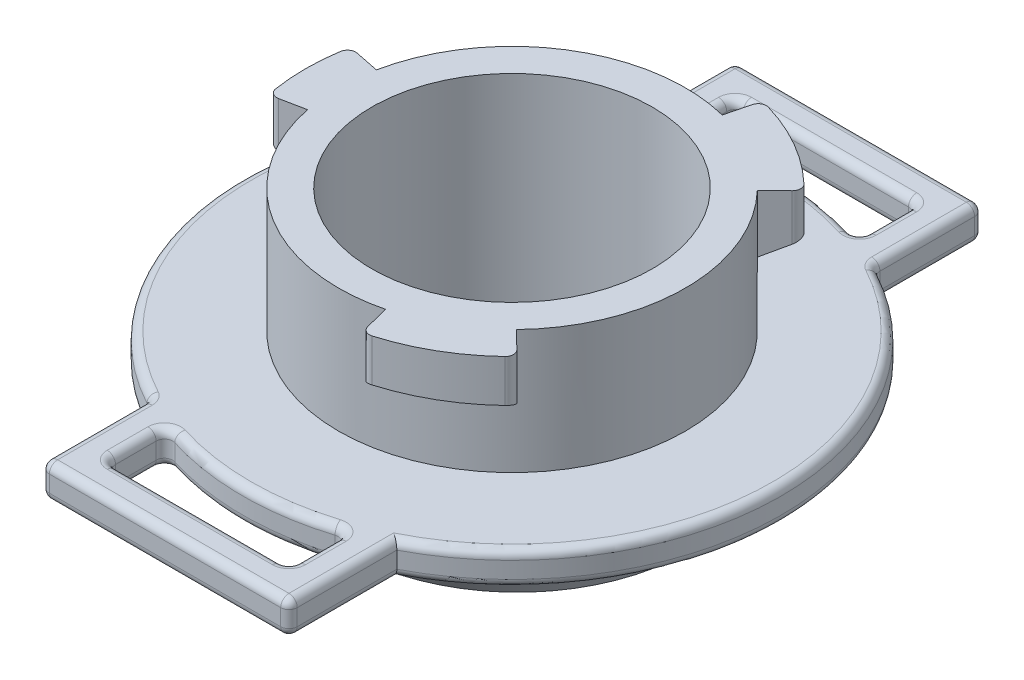
SolidWorks part; units mm, degrees
ref_plane "Front" through (0, 0, 0) normal (0, 0, 1) x (1, 0, 0)
ref_plane "Top" through (0, 0, 0) normal (0, 1, 0) x (1, 0, 0)
ref_plane "Right" through (0, 0, 0) normal (1, 0, 0) x (0, 0, -1)
sketch "Sketch1" plane through (0, 0, 0) normal (0, 0, 1) x (1, 0, 0)
  line L0 (-159.7123, 0) -> (16.3, 0) construction
  line L1 (0, 78.8071) -> (0, -67.8786) construction
  line L2 (9.2, 9.5) -> (9.2, 0)
  line L3 (9.2, 0) -> (16.3, 0)
  line L7 (16.3, 2) -> (10.5, 2)
  line L8 (10.5, 2) -> (10.5, 9.5)
  line L9 (10.5, 9.5) -> (9.2, 9.5)
  line L11 (-10.5, 6) -> (-12.5, 6.9326)
  line L12 (-10.5, 9.5) -> (-12.5, 9.5)
  line L13 (-10.5, 9.5) -> (-10.5, 6)
  line L14 (-10.5, 6) -> (-12.5, 6)
  line L15 (-12.5, 9.5) -> (-12.5, 6)
  line L19 (16.3, 2) -> (16.3, 0)
  line L20 (9.2, 9.5) -> (0, 9.5)
  line L21 (0, 9.5) -> (0, 0)
  line L22 (0, 0) -> (9.2, 0)
  dimension "D10" = 2
  dimension "D1" = 21
  dimension "D2" = 1.3
  dimension "D3" = 7.5
  dimension "D4" = 2
  dimension "D9" = 3.5
  dimension "D11" = 25
revolve "Revolve1" add sketch "Sketch1" angle 360 about L1 region at (9.85, 9.3814, 0) region at (4.6, 4.75, 0)
ref_plane "Plane1" through (0, 2, 0) normal (0, 1, 0) x (1, 0, 0)
sketch "Sketch3" plane through (0, 2, 0) normal (0, 1, 0) x (1, 0, 0)
  line L0 (-23.4994, 0) -> (28.8789, 0) construction
  line L1 (0, 22.41) -> (0, -22.0852) construction
  line L3 (2, 20) -> (3, 20)
  line L4 (2, 20) -> (2, 15)
  line L5 (2, 15) -> (3, 15)
  line L6 (3, 20) -> (3, 15)
  line L7 (-2, 20) -> (-3, 20)
  line L8 (-2, 20) -> (-2, 15)
  line L9 (-2, 15) -> (-3, 15)
  line L10 (-3, 20) -> (-3, 15)
  dimension "D1" = 4
  dimension "D2" = 1
  dimension "D3" = 20
  dimension "D4" = 15
revolve "Revolve2" add sketch "Sketch1<7>" angle 22.9 mid plane about L1 region at (-11.4488, 7.9712, 0)
sketch "Sketch1<7>" plane through (0, 0, 0) normal (0, 0, 1) x (1, 0, 0) same geometry as "Sketch1"
ref_axis "Axis1" through (0, -50, 0) along (0, 1, 0)
ref_plane "Plane2" through (0, 0, 0) normal (-0.866, 0, -0.5) x (0, 1, 0)
sketch "Sketch4" plane through (0, 0, 0) normal (-0.866, 0, -0.5) x (0, 1, 0)
  line L1 (9.5, 10.5) -> (6, 10.5)
  line L2 (9.5, 10.5) -> (9.5, 12.5)
  line L3 (9.5, 12.5) -> (6, 12.5)
  line L4 (6, 10.5) -> (6, 12.5)
  dimension "D1" = 2
  dimension "D2" = 3.5
revolve "Revolve3" add sketch "Sketch4" angle 32 mid plane about axis through (0, -50, 0) along (0, 1, 0)
mirror "Mirror1" about plane through (0, 0, 0) normal (0, 0, 1) of "Revolve3"
fillet "Fillet2" radius 0.5 6 edges at (3.024, 7.75, -12.1287) (8.9917, 7.75, -8.6832) (8.9917, 7.75, 8.6832) (3.024, 7.75, 12.1287) (-12.2512, 8.2163, -2.4814) (-12.2512, 8.2163, 2.4814)
revolve "Cut-Revolve1" cut sketch "Sketch1<9>" angle 360 about axis through (0, -50, 0) along (0, 1, 0) region at (-11.8333, 6.3109, 0)
sketch "Sketch1<9>" plane through (0, 0, 0) normal (0, 0, 1) x (1, 0, 0) same geometry as "Sketch1"
sketch "Sketch5" plane through (0, 0, 0) normal (0, -1, 0) x (1, 0, 0)
  circle A0 centre (0, 0) radius 11
  dimension "D1" = 22
sketch "Sketch21" plane through (0, 0, 0) normal (0, 1, 0) x (1, 0, 0)
  line L1 (-7.5, 21) -> (7.5, 21)
  line L2 (-7.5, 21) -> (-7.5, -21)
  line L3 (-7.5, -21) -> (7.5, -21)
  line L4 (7.5, 21) -> (7.5, -21)
  line L5 (-5.5, 19) -> (5.5, 19)
  line L6 (-5.5, 19) -> (-5.5, -19)
  line L7 (-5.5, -19) -> (5.5, -19)
  line L8 (5.5, 19) -> (5.5, -19)
  circle A2 centre (0, 0) radius 16.3
  circle A3 centre (0, 0) radius 16.3 construction
  dimension "D1" = 2
  dimension "D2" = 2
  dimension "D3" = 2
  dimension "D4" = 2
  dimension "D5" = 42
  dimension "D6" = 11
  dimension "D7" = 5.5
  dimension "D8" = 21
extrude "Boss-Extrude7" add sketch "Sketch21" along normal up to surface (2 mm away) contours A2 L8 L7 L6 L2 L3 L4 | A2 L4 L1 L2 L6 L5 L8 region at (0, 0, -20.8364) region at (-6.58, 0, 15.0915) up to face at (0, 2, 10.5)
fillet "Fillet6" radius 0.5 47 edges at (-5.5, 0, -17.172) (-5.5, 0, 17.172) (5.5, 0, -17.172) (5.5, 0, 17.172) (0, 0, -19) (0, 0, 19) (0, 0, 21) (0, 2, 21) (0, 2, -21) (0, 2, -19) (-5.5, 2, -17.172) (0, 2, 19) (5.5, 2, -17.172) (5.5, 2, 17.172) (7.5, 2, 17.736) (7.5, 2, -17.736) (0, 0, -21) (7.5, 1, -21) (7.5, 1, 21) (7.5, 0, -17.736) (7.5, 0, 17.736) (-7.5, 0, 17.736) (0, 0, -16.3) (-16.3, 0, 0) (-16.3, 2, 0) (16.3, 2, 0) (16.3, 0, 0) (0, 2, -16.3) (0, 0, 16.3) (0, 2, 16.3) (-5.5, 1, -19) (5.5, 1, -19) (5.5, 1, -15.3441) (-7.5, 1, 21) (-7.5, 0, -17.736) (-7.5, 1, -14.472) (-7.5, 1, 14.472) (7.5, 1, -14.472) (-7.5, 1, -21) (-5.5, 1, -15.3441) (-5.5, 1, 19) (-5.5, 1, 15.3441) (5.5, 1, 15.3441) (-7.5, 2, 17.736) (-5.5, 2, 17.172) (-7.5, 2, -17.736) (5.5, 1, 19)
sketch "Sketch22" plane through (0, 0, 0) normal (0, -1, 0) x (-1, 0, 0)
  circle A0 centre (0, 0) radius 9.75
  dimension "D1" = 19.5
extrude "Boss-Extrude8" add sketch "Sketch22" along normal blind 3.4937 draft 1
sketch "Sketch23" plane through (0, -3.4937, 0) normal (0, -1, 0) x (-1, 0, 0)
  circle A0 centre (0, 0) radius 8.489
  circle A1 centre (0, 0) radius 9.689 construction
  dimension "D1" = 1.2
extrude "Cut-Extrude1" cut sketch "Sketch23" against normal through all
sketch "Sketch24" plane through (0, -3.4937, 0) normal (0, -1, 0) x (-1, 0, 0)
  circle A0 centre (0, 0.333) radius 11
  circle A1 centre (0, 0) radius 8.489
  circle A2 centre (0, 0) radius 8.489 construction
  point P6 (0, 0)
  dimension "D1" = 22
extrude "Boss-Extrude9" add sketch "Sketch24" along normal blind 1 draft 30
